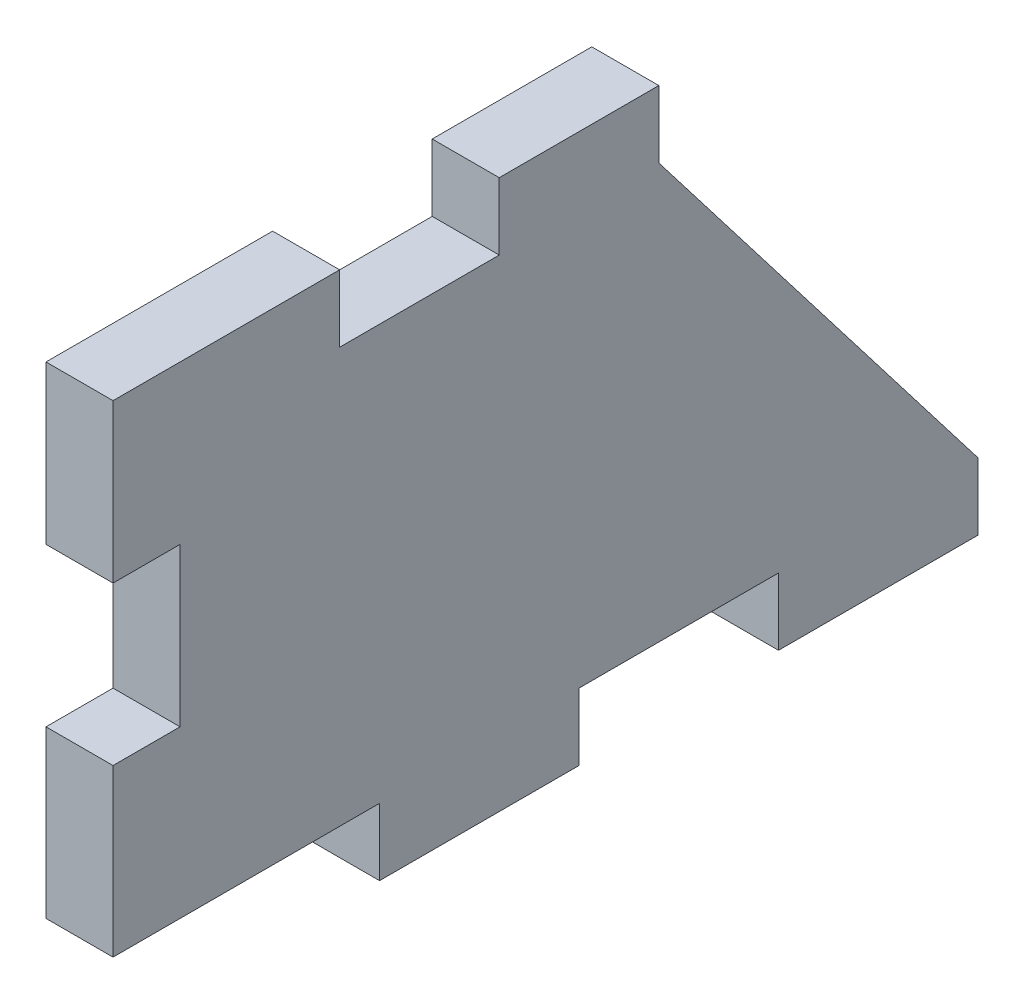
SolidWorks part; units mm, degrees
ref_plane "Front Plane" through (0, 0, 0) normal (0, 0, 1) x (1, 0, 0)
ref_plane "Top Plane" through (0, 0, 0) normal (0, 1, 0) x (1, 0, 0)
ref_plane "Right Plane" through (0, 0, 0) normal (1, 0, 0) x (0, 0, -1)
sketch "Sketch1" plane through (0, 0, 0) normal (1, 0, 0) x (0, 0, -1)
  line L1 (-31.75, -16.51) -> (31.75, -16.51)
  line L2 (-31.75, -16.51) -> (-31.75, 16.51)
  line L3 (-31.75, 16.51) -> (31.75, 16.51)
  line L4 (31.75, -16.51) -> (31.75, 16.51)
  line L5 (-31.75, -16.51) -> (31.75, 16.51) construction
  line L6 (-31.75, 16.51) -> (31.75, -16.51) construction
  point P0 (0, 0)
  dimension "D1" = 33.02
  dimension "D2" = 63.5
extrude "Boss-Extrude1" add sketch "Sketch1" along normal blind 5.334
sketch "Sketch2" plane through (0, 0, 0) normal (-1, 0, 0) x (0, 0, 1)
  line L1 (-31.75, -16.51) -> (-31.75, 16.51)
  line L5 (-31.75, 16.51) -> (31.75, 16.51) construction
  line L18 (-31.75, -16.51) -> (-6.35, 16.51)
  line L19 (-6.35, 16.51) -> (-31.75, 16.51)
extrude "Cut-Extrude1" cut sketch "Sketch2" against normal through all
sketch "Sketch3" plane through (0, 0, 0) normal (-1, 0, 0) x (0, 0, 1)
  line L1 (31.75, 16.51) -> (19.05, 16.51)
  line L2 (31.75, 16.51) -> (31.75, 21.844)
  line L3 (31.75, 21.844) -> (19.05, 21.844)
  line L4 (19.05, 16.51) -> (19.05, 21.844)
  line L5 (-6.35, 16.51) -> (6.35, 16.51)
  line L6 (-6.35, 16.51) -> (-6.35, 21.844)
  line L7 (-6.35, 21.844) -> (6.35, 21.844)
  line L8 (6.35, 16.51) -> (6.35, 21.844)
  line L9 (31.75, -16.51) -> (31.75, -21.844) construction
  line L10 (31.75, -21.844) -> (15.875, -21.844) construction
  line L11 (31.75, -16.51) -> (-31.75, -16.51) construction
  line L12 (15.875, -16.51) -> (0, -16.51)
  line L13 (15.875, -16.51) -> (15.875, -21.844)
  line L14 (15.875, -21.844) -> (0, -21.844)
  line L15 (0, -16.51) -> (0, -21.844)
  line L16 (0, -21.844) -> (-15.875, -21.844) construction
  line L17 (6.35, 21.844) -> (19.05, 21.844) construction
  line L18 (-31.75, -16.51) -> (-15.875, -16.51)
  line L19 (-31.75, -16.51) -> (-31.75, -21.844)
  line L20 (-31.75, -21.844) -> (-15.875, -21.844)
  line L21 (-15.875, -16.51) -> (-15.875, -21.844)
  dimension "D2" = 5.334
  dimension "material" = 5.334
extrude "Boss-Extrude2" add sketch "Sketch3" against normal through all
sketch "Sketch4" plane through (0, 0, 0) normal (-1, 0, 0) x (0, 0, 1)
  line L2 (31.75, 21.844) -> (31.75, -16.51) construction
  line L3 (31.75, -15.875) -> (37.084, -15.875)
  line L4 (31.75, -15.875) -> (31.75, 21.209)
  line L5 (31.75, 21.209) -> (37.084, 21.209)
  line L6 (37.084, -15.875) -> (37.084, 21.209)
  dimension "D1" = 5.334
extrude "Boss-Extrude7" add sketch "Sketch4" against normal blind 5.334
sketch "Sketch5" plane through (5.334, 0, 0) normal (1, 0, 0) x (0, 0, -1)
  line L1 (-37.084, -15.875) -> (-37.084, 21.209) construction
  line L2 (-37.084, -3.302) -> (-31.75, -3.302)
  line L3 (-37.084, -3.302) -> (-37.084, 9.271)
  line L4 (-37.084, 9.271) -> (-31.75, 9.271)
  line L5 (-31.75, -3.302) -> (-31.75, 9.271)
  line L6 (-31.75, 9.271) -> (-31.75, 21.844) construction
  line L7 (-31.75, 21.844) -> (-19.05, 21.844) construction
  line L8 (-31.75, -3.302) -> (-31.75, -15.875) construction
extrude "Cut-Extrude2" cut sketch "Sketch5" against normal through all
sketch "Sketch6" plane through (5.334, 0, 0) normal (1, 0, 0) x (0, 0, -1)
  line L1 (-37.084, 21.209) -> (-31.75, 21.209)
  line L2 (-37.084, 21.209) -> (-37.084, 21.844)
  line L3 (-37.084, 21.844) -> (-31.75, 21.844)
  line L4 (-31.75, 21.209) -> (-31.75, 21.844)
extrude "Boss-Extrude9" add sketch "Sketch6" against normal blind 5.334
sketch "Sketch7" plane through (5.334, 0, 0) normal (1, 0, 0) x (0, 0, -1)
  line L0 (-31.75, -15.875) -> (-31.75, -16.51) construction
  line L1 (-31.75, -16.51) -> (-37.084, -16.51)
  line L2 (-31.75, -16.51) -> (-31.75, -15.875)
  line L3 (-31.75, -15.875) -> (-37.084, -15.875)
  line L4 (-37.084, -16.51) -> (-37.084, -15.875)
extrude "Boss-Extrude10" add sketch "Sketch7" against normal blind 5.334
equation "\"D1@Boss-Extrude1\" = \"material\""
equation "\"D1@Boss-Extrude7\"=\"material\""
equation "\"material\"=\"GMaterial@Platform.assembly\""
equation "\"D1@Boss-Extrude9\" = \"material\""
equation "\"D1@Boss-Extrude10\" = \"material\""
